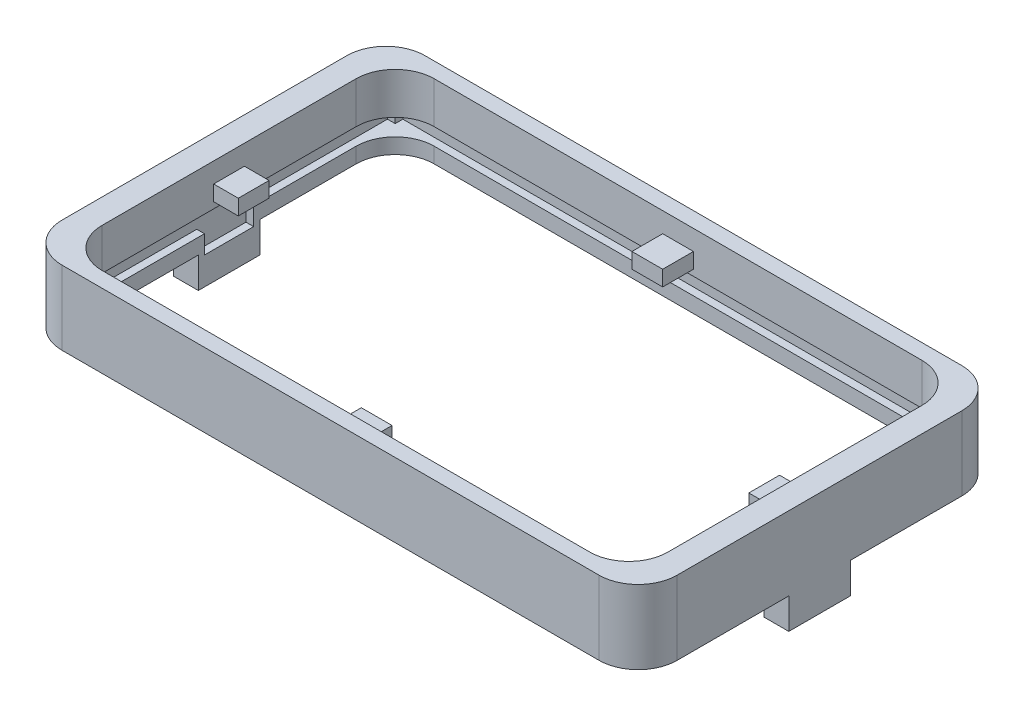
SolidWorks part; units mm, degrees
ref_plane "Front Plane" through (0, 0, 0) normal (0, 0, 1) x (1, 0, 0)
ref_plane "Top Plane" through (0, 0, 0) normal (0, 1, 0) x (1, 0, 0)
ref_plane "Right Plane" through (0, 0, 0) normal (1, 0, 0) x (0, 0, -1)
sketch "Sketch1" plane through (0, 0, 0) normal (0, 1, 0) x (1, 0, 0)
  line L1 (-50, 29.5) -> (50, 29.5)
  line L2 (-50, 29.5) -> (-50, -29.5)
  line L3 (-50, -29.5) -> (50, -29.5)
  line L4 (50, 29.5) -> (50, -29.5)
  line L5 (-50, 29.5) -> (50, -29.5) construction
  line L6 (-50, -29.5) -> (50, 29.5) construction
  point P0 (0, 0)
  dimension "D1" = 100
  dimension "D2" = 59
extrude "Boss-Extrude1" add sketch "Sketch1" along normal blind 12
sketch "Sketch2" plane through (0, 12, 0) normal (0, 1, 0) x (1, 0, 0)
  line L1 (-46, 27) -> (46, 27)
  line L2 (-46, 27) -> (-46, -27)
  line L3 (-46, -27) -> (46, -27)
  line L4 (46, 27) -> (46, -27)
  line L5 (-46, 27) -> (46, -27) construction
  line L6 (-46, -27) -> (46, 27) construction
  point P0 (0, 0)
  dimension "D1" = 54
  dimension "D2" = 92
extrude "Cut-Extrude1" cut sketch "Sketch2" against normal through all
sketch "Sketch3" plane through (-46, 0, 0) normal (1, 0, 0) x (0, 0, -1)
  line L0 (0, 0) -> (0, 12) construction
  line L1 (27, 0) -> (-27, 0) construction
  line L2 (27, 12) -> (-27, 12) construction
  line L3 (-27, 0) -> (-27, 12) construction
  line L4 (27, 2.5) -> (-27, 2.5)
  line L5 (27, 2.5) -> (27, 5.25)
  line L6 (27, 5.25) -> (-27, 5.25)
  line L7 (-27, 2.5) -> (-27, 5.25)
  line L8 (27, 2.5) -> (-27, 5.25) construction
  line L9 (27, 5.25) -> (-27, 2.5) construction
  point P6 (0, 3.875)
  dimension "D1" = 2.5
  dimension "D2" = 2.75
  dimension "D3" = 0
extrude "Cut-Extrude2" cut sketch "Sketch3" against normal blind 1.25
sketch "Sketch4" plane through (46, 0, 0) normal (-1, 0, 0) x (0, 0, 1)
  line L0 (0, 0) -> (0, 12) construction
  line L1 (27, 0) -> (-27, 0) construction
  line L2 (27, 12) -> (-27, 12) construction
  line L3 (27, 0) -> (27, 12) construction
  line L4 (27, 2.5) -> (-27, 2.5)
  line L5 (27, 2.5) -> (27, 5.25)
  line L6 (27, 5.25) -> (-27, 5.25)
  line L7 (-27, 2.5) -> (-27, 5.25)
  line L8 (27, 2.5) -> (-27, 5.25) construction
  line L9 (27, 5.25) -> (-27, 2.5) construction
  point P6 (0, 3.875)
  dimension "D1" = 2.5
  dimension "D2" = 0
  dimension "D3" = 2.75
extrude "Cut-Extrude3" cut sketch "Sketch4" against normal blind 1.25
sketch "Sketch5" plane through (0, 0, -27) normal (0, 0, 1) x (1, 0, 0)
  line L0 (0, 0) -> (0, 12) construction
  line L1 (46, 0) -> (-46, 0) construction
  line L2 (46, 12) -> (-46, 12) construction
  line L3 (-46, 0) -> (-46, 2.5) construction
  line L4 (46, 5.25) -> (-46, 5.25)
  line L5 (46, 5.25) -> (46, 2.5)
  line L6 (46, 2.5) -> (-46, 2.5)
  line L7 (-46, 5.25) -> (-46, 2.5)
  line L8 (46, 5.25) -> (-46, 2.5) construction
  line L9 (46, 2.5) -> (-46, 5.25) construction
  point P6 (0, 3.875)
  dimension "D1" = 2.5
  dimension "D2" = 2.75
extrude "Cut-Extrude4" cut sketch "Sketch5" against normal blind 1.25
sketch "Sketch6" plane through (0, 0, 27) normal (0, 0, -1) x (-1, 0, 0)
  line L0 (0, 0) -> (0, 12) construction
  line L1 (46, 0) -> (-46, 0) construction
  line L2 (46, 12) -> (-46, 12) construction
  line L3 (46, 0) -> (46, 2.5) construction
  line L4 (-46, 5.25) -> (46, 5.25)
  line L5 (-46, 5.25) -> (-46, 2.5)
  line L6 (-46, 2.5) -> (46, 2.5)
  line L7 (46, 5.25) -> (46, 2.5)
  line L8 (-46, 5.25) -> (46, 2.5) construction
  line L9 (-46, 2.5) -> (46, 5.25) construction
  point P6 (0, 3.875)
  dimension "D1" = 2.75
  dimension "D2" = 2.5
extrude "Cut-Extrude5" cut sketch "Sketch6" against normal blind 1.25
fillet "Fillet1" radius 1 2 edges at (0, 5.25, -28.25) (0, 5.25, 28.25)
sketch "Sketch7" plane through (0, 0, 0) normal (0, -1, 0) x (1, 0, 0)
  line L0 (-50, 0) -> (-46, 0) construction
  line L1 (-50, -29.5) -> (-50, 29.5) construction
  line L2 (-46, -27) -> (-46, 27) construction
  line L4 (-50, -5) -> (-46, -5)
  line L5 (-50, -5) -> (-50, 5)
  line L6 (-50, 5) -> (-46, 5)
  line L7 (-46, -5) -> (-46, 5)
  line L8 (-50, -5) -> (-46, 5) construction
  line L9 (-50, 5) -> (-46, -5) construction
  point P6 (-48, 0)
  dimension "D1" = 10
extrude "Boss-Extrude2" add sketch "Sketch7" along normal blind 5
mirror "Mirror2" about plane through (0, 0, 0) normal (1, 0, 0) of "Boss-Extrude2"
sketch "Sketch8" plane through (-46, 0, 0) normal (1, 0, 0) x (0, 0, -1)
  line L0 (-27, 2.5) -> (27, 2.5) construction
  line L1 (4, 2.5) -> (-4, 2.5)
  line L2 (4, 2.5) -> (4, -0.5)
  line L3 (4, -0.5) -> (-4, -0.5)
  line L4 (-4, 2.5) -> (-4, -0.5)
  line L5 (0, -5) -> (0, 2.5) construction
  line L6 (5, -5) -> (-5, -5) construction
  dimension "D1" = 8
  dimension "D2" = 4
  dimension "D3" = 3
extrude "Cut-Extrude6" cut sketch "Sketch8" against normal up to surface and the other way up to surface up to face at (-47.25, 3.875, 0) other way up to face at (47.25, 3.875, 0)
fillet "Fillet2" radius 6.35 8 edges at (-46, 1.25, -27) (-50, 6, -29.5) (-50, 6, 29.5) (50, 6, 29.5) (46, 1.25, -27) (50, 6, -29.5) (-46, 1.25, 27) (46, 1.25, 27)
sketch "Sketch9" plane through (0, 0, 27) normal (0, 0, -1) x (-1, 0, 0)
  line L0 (0, 12) -> (0, 5.25) construction
  line L1 (39.65, 12) -> (-39.65, 12) construction
  line L2 (39.65, 5.25) -> (-39.65, 5.25) construction
  line L3 (-46, 5.25) -> (46, 5.25) construction
  line L4 (-2.5, 6.25) -> (2.5, 6.25)
  line L5 (-2.5, 6.25) -> (-2.5, 8.75)
  line L6 (-2.5, 8.75) -> (2.5, 8.75)
  line L7 (2.5, 6.25) -> (2.5, 8.75)
  line L8 (-2.5, 6.25) -> (2.5, 8.75) construction
  line L9 (-2.5, 8.75) -> (2.5, 6.25) construction
  point P6 (0, 7.5)
  dimension "D1" = 1
  dimension "D2" = 2.5
  dimension "D3" = 5
extrude "Boss-Extrude3" add sketch "Sketch9" along normal blind 5
sketch "Sketch10" plane through (0, 0, -27) normal (0, 0, 1) x (1, 0, 0)
  line L0 (0, 12) -> (0, 5.25) construction
  line L1 (39.65, 12) -> (-39.65, 12) construction
  line L2 (39.65, 5.25) -> (-39.65, 5.25) construction
  line L4 (2.5, 6.25) -> (-2.5, 6.25)
  line L5 (2.5, 6.25) -> (2.5, 8.75)
  line L6 (2.5, 8.75) -> (-2.5, 8.75)
  line L7 (-2.5, 6.25) -> (-2.5, 8.75)
  line L8 (2.5, 6.25) -> (-2.5, 8.75) construction
  line L9 (2.5, 8.75) -> (-2.5, 6.25) construction
  point P6 (0, 7.5)
  dimension "D1" = 5
  dimension "D2" = 2.5
  dimension "D3" = 1
extrude "Boss-Extrude4" add sketch "Sketch10" along normal blind 5
sketch "Sketch11" plane through (46, 0, 0) normal (-1, 0, 0) x (0, 0, 1)
  line L0 (0, 12) -> (0, 5.25) construction
  line L1 (20.65, 12) -> (-20.65, 12) construction
  line L2 (20.65, 5.25) -> (-20.65, 5.25) construction
  line L4 (-2.5, 6.25) -> (2.5, 6.25)
  line L5 (-2.5, 6.25) -> (-2.5, 8.75)
  line L6 (-2.5, 8.75) -> (2.5, 8.75)
  line L7 (2.5, 6.25) -> (2.5, 8.75)
  line L8 (-2.5, 6.25) -> (2.5, 8.75) construction
  line L9 (-2.5, 8.75) -> (2.5, 6.25) construction
  point P6 (0, 7.5)
  dimension "D1" = 1
  dimension "D2" = 2.5
  dimension "D3" = 5
extrude "Boss-Extrude5" add sketch "Sketch11" along normal blind 5
sketch "Sketch12" plane through (-46, 0, 0) normal (1, 0, 0) x (0, 0, -1)
  line L0 (0, 12) -> (0, 5.25) construction
  line L1 (20.65, 12) -> (-20.65, 12) construction
  line L2 (20.65, 5.25) -> (-20.65, 5.25) construction
  line L4 (-2.5, 6.25) -> (2.5, 6.25)
  line L5 (-2.5, 6.25) -> (-2.5, 8.75)
  line L6 (-2.5, 8.75) -> (2.5, 8.75)
  line L7 (2.5, 6.25) -> (2.5, 8.75)
  line L8 (-2.5, 6.25) -> (2.5, 8.75) construction
  line L9 (-2.5, 8.75) -> (2.5, 6.25) construction
  point P6 (0, 7.5)
  dimension "D1" = 5
  dimension "D2" = 2.5
  dimension "D3" = 1
extrude "Boss-Extrude6" add sketch "Sketch12" along normal blind 4
